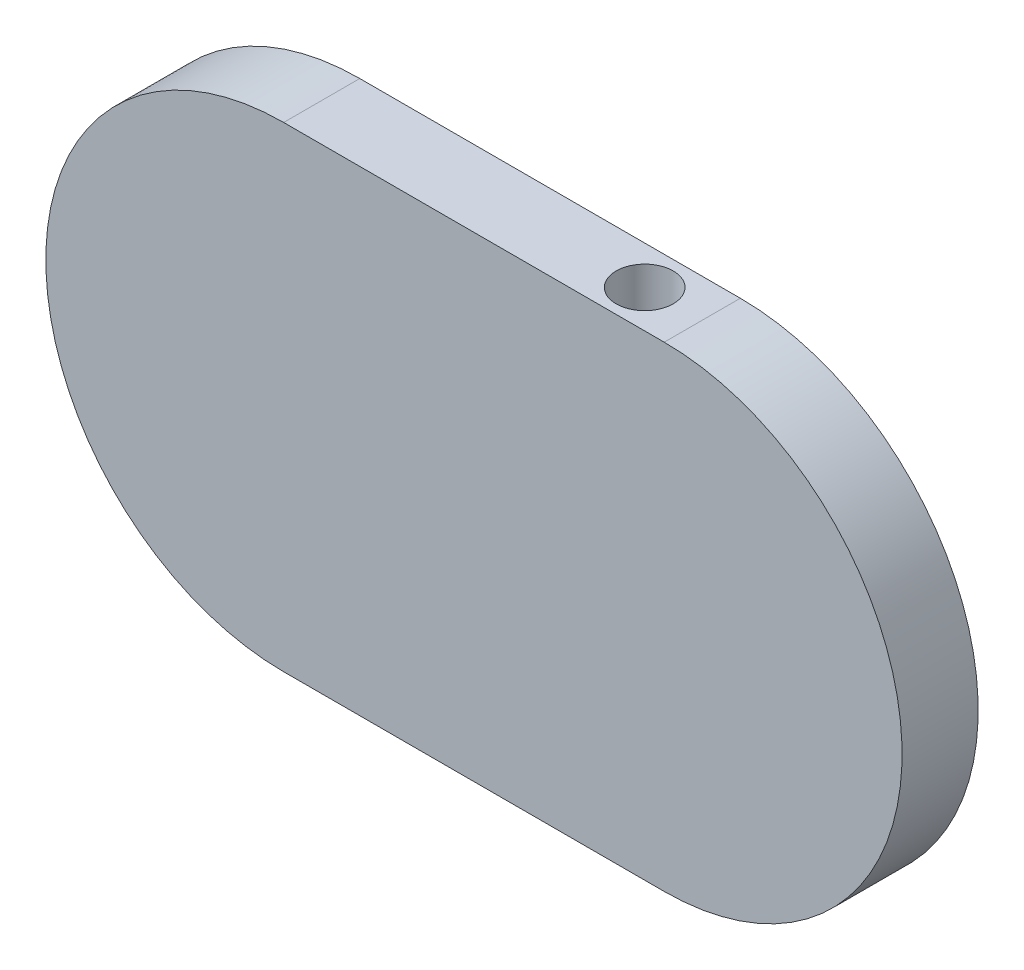
SolidWorks part; units mm, degrees
ref_plane "Front Plane" through (0, 0, 0) normal (0, 0, 1) x (1, 0, 0)
ref_plane "Top Plane" through (0, 0, 0) normal (0, 1, 0) x (1, 0, 0)
ref_plane "Right Plane" through (0, 0, 0) normal (1, 0, 0) x (0, 0, -1)
sketch "Sketch1" plane through (0, 0, 0) normal (0, 0, 1) x (1, 0, 0)
  line L0 (-37.3008, 0) -> (362.6992, 0) construction
  line L1 (-37.3008, 250) -> (362.6992, 250)
  line L2 (-37.3008, -250) -> (362.6992, -250)
  arc A0 (-37.3008, 250) -> (-37.3008, -250) centre (-37.3008, 0) ccw
  arc A1 (362.6992, -250) -> (362.6992, 250) centre (362.6992, 0) ccw
  point P3 (162.6992, 0)
  dimension "D1" = 400
  dimension "D2" = 500
extrude "Boss-Extrude1" add sketch "Sketch1" along normal blind 80
sketch "Sketch2" plane through (0, 250, 0) normal (0, 1, 0) x (1, 0, 0)
  circle A0 centre (302.5494, -40.4093) radius 30
extrude "Cut-Extrude1" cut sketch "Sketch2" against normal through all
sketch "Sketch4" plane through (0, 0, 0) normal (0, 0, -1) x (-1, 0, 0)
  circle A0 centre (125.2443, 0) radius 97
extrude "Boss-Extrude3" add sketch "Sketch4" along normal blind 80
fillet "Fillet1" radius 81.12 1 edges at (-222.2443, 0, -80)
